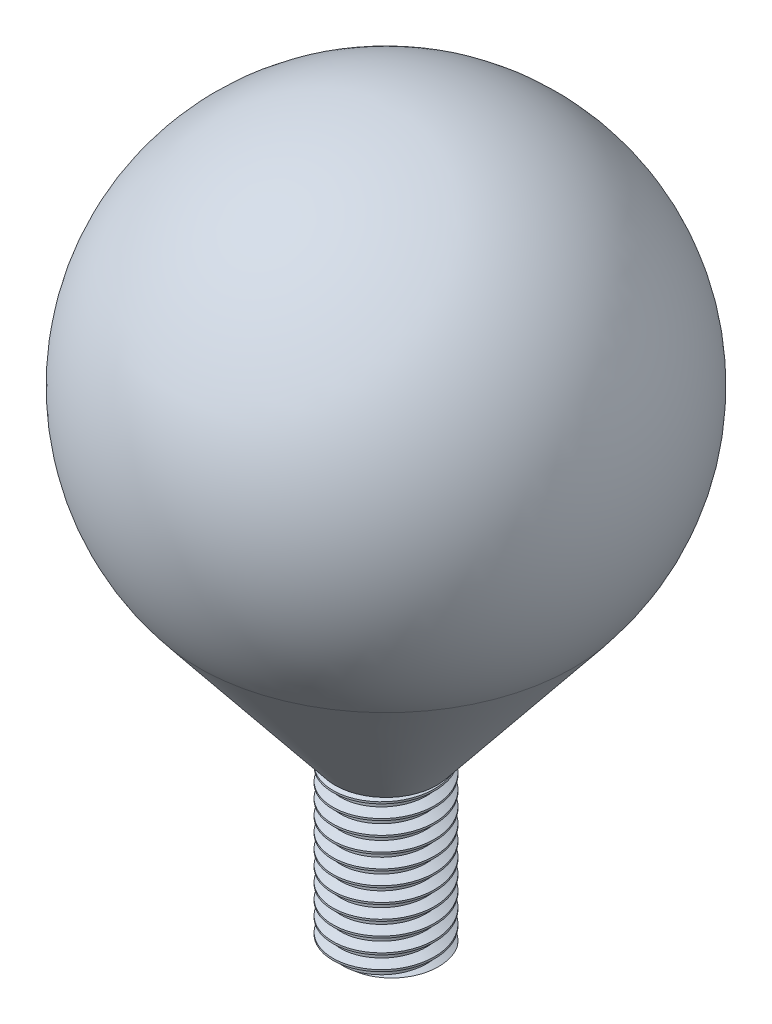
SolidWorks part; units mm, degrees
ref_plane "Front Plane" through (0, 0, 0) normal (0, 0, 1) x (1, 0, 0)
ref_plane "Top Plane" through (0, 0, 0) normal (0, 1, 0) x (1, 0, 0)
ref_plane "Right Plane" through (0, 0, 0) normal (1, 0, 0) x (0, 0, -1)
sketch "Sketch1" plane through (0, 0, 0) normal (0, 0, 1) x (1, 0, 0)
  line L0 (0, -260.4644) -> (0, 12762.7567) construction
  line L1 (-3.175, -20) -> (-3.175, -30)
  line L2 (-3.175, -30) -> (0, -30)
  line L5 (-3.175, -20) -> (-11.6945, -9.3935)
  line L6 (0, 15) -> (0, -30)
  arc A0 (0, 15) -> (-11.6945, -9.3935) centre (0, 0) ccw
  dimension "D3" = 15
  dimension "D1" = 10
  dimension "D2" = 3.175
  dimension "D4" = 30
revolve "Revolve1" add sketch "Sketch1" angle 360 about L0
thread "Thread2" pitch 0.9071 method cut profile "Thread Profile2" start angle 0, offset 1, length 0, pitch 0.9071, diameter 6.35
ref_plane "Plane2" through (3.175, -31, 0) normal (0, 0, 1) x (1, 0, 0)
sketch "Thread Profile2" plane through (3.175, -31, 0) normal (0, 0, 1) x (1, 0, 0)
  line L0 (0, 0) -> (0, 0.9071) construction
  line L11 (0, 0) -> (0, 0.7937)
  line L12 (0, 0.7937) -> (-0.491, 0.5103)
  line L13 (-0.491, 0.5103) -> (-0.491, 0.2835)
  line L15 (-0.491, 0.2835) -> (0, 0)
  line L17 (-0.491, 0.3969) -> (0, 0.3969) construction
  point P2 (0, 0)
  dimension "Pitch" = 0.9071
  dimension "Profile_Angle" = 60
  dimension "Profile_Land" = 0.2268
  dimension "Profile_Height" = 0.491
